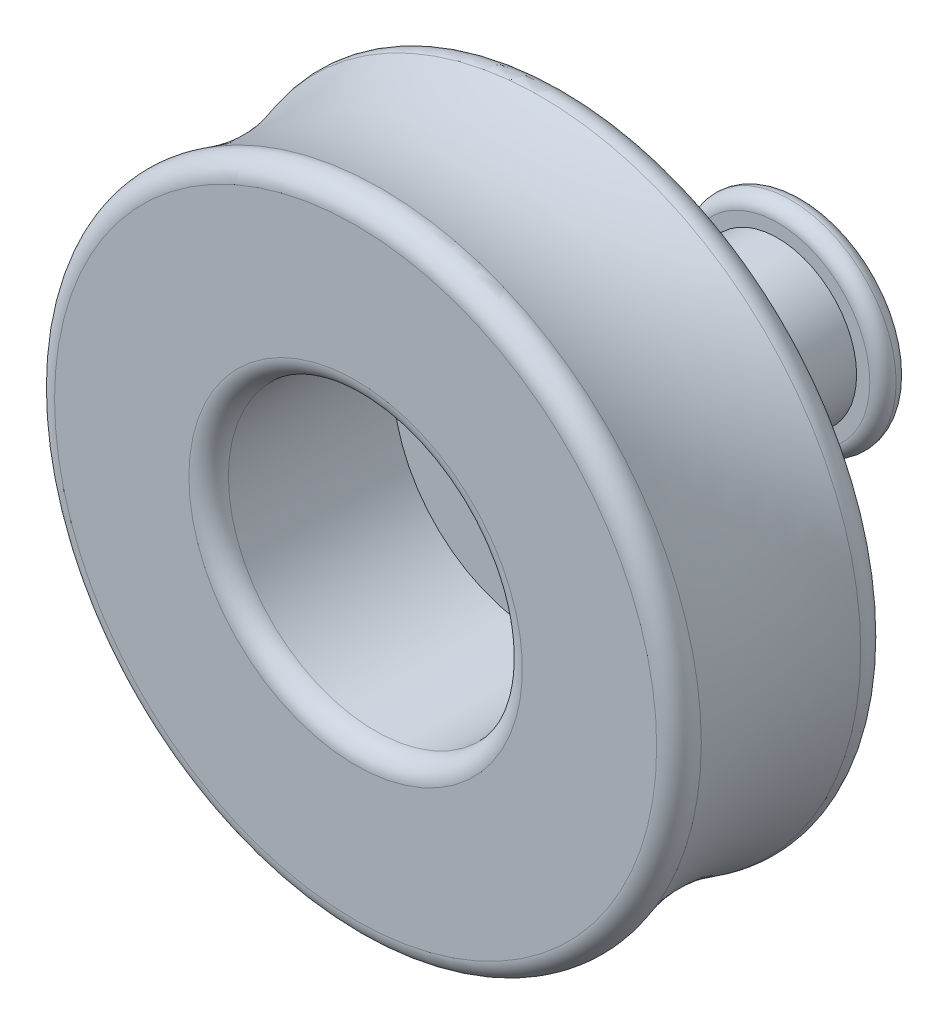
SolidWorks part; units mm, degrees
ref_plane "Front Plane" through (0, 0, 0) normal (0, 0, 1) x (1, 0, 0)
ref_plane "Top Plane" through (0, 0, 0) normal (0, 1, 0) x (1, 0, 0)
ref_plane "Right Plane" through (0, 0, 0) normal (1, 0, 0) x (0, 0, -1)
sketch "Sketch2" plane through (0, 0, 0) normal (0, 1, 0) x (1, 0, 0)
  line L1 (-12.5, -8) -> (12.5, -8)
  line L2 (-12.5, -8) -> (-12.5, 8)
  line L3 (-12.5, 8) -> (12.5, 8)
  line L4 (12.5, -8) -> (12.5, 8)
  line L5 (-12.5, -8) -> (12.5, 8) construction
  line L6 (-12.5, 8) -> (12.5, -8) construction
  line L7 (12.5, 8) -> (6.5, 8)
  line L8 (12.5, 8) -> (12.5, 15)
  line L9 (12.5, 15) -> (6.5, 15)
  line L10 (6.5, 8) -> (6.5, 15)
  line L11 (12.5, 15) -> (4.5, 15)
  line L12 (12.5, 15) -> (12.5, 17)
  line L13 (12.5, 17) -> (4.5, 17)
  line L14 (4.5, 15) -> (4.5, 17)
  line L15 (12.5, 17) -> (6.5, 17)
  line L16 (12.5, 17) -> (12.5, 24)
  line L17 (12.5, 24) -> (6.5, 24)
  line L18 (6.5, 17) -> (6.5, 24)
  line L19 (12.5, 24) -> (4.5, 24)
  line L20 (12.5, 24) -> (12.5, 26)
  line L21 (12.5, 26) -> (4.5, 26)
  line L22 (4.5, 24) -> (4.5, 26)
  arc A0 (-12.5, 8) -> (-12.5, -8) centre (-30.8303, 0) cw
  point P0 (0, 0)
  dimension "D7" = 7
  dimension "D1" = 7
  dimension "D2" = 16
  dimension "D3" = 25
  dimension "D4" = 6
  dimension "D5" = 8
  dimension "D6" = 2
  dimension "D8" = 6
  dimension "D9" = 8
  dimension "D10" = 2
revolve "Revolve1" add sketch "Sketch2" angle 360 about L4 region at (0.5563, 0, 0) region at (9.5, 0, -11.5) region at (8.5, 0, -16) region at (9.5, 0, -20.5) region at (8.5, 0, -25)
sketch "Sketch3" plane through (0, 0, 8) normal (0, 0, 1) x (1, 0, 0)
  circle A0 centre (12.5, 0) radius 11.15
  circle A1 centre (12.5, 0) radius 25 construction
  dimension "D1" = 22.3
extrude "Cut-Extrude1" cut sketch "Sketch3" against normal blind 14
sketch "Sketch8" plane through (0, 0, -6) normal (0, 0, 1) x (1, 0, 0)
  circle A0 centre (12.5, 0) radius 4.25
  circle A1 centre (12.5, 0) radius 11.15 construction
  dimension "D1" = 8.5
extrude "Cut-Extrude3" cut sketch "Sketch8" against normal through all
fillet "Fillet1" radius 1.5 1 edges at (16.75, 0, -6)
fillet "Fillet2" radius 1.5 3 edges at (37.5, 0, -8) (37.5, 0, 8) (23.65, 0, 8)
fillet "Fillet3" radius 1 4 edges at (20.5, 0, -15) (20.5, 0, -17) (20.5, 0, -24) (20.5, 0, -26)
fillet "Fillet4" radius 1.5 1 edges at (16.75, 0, -26)
